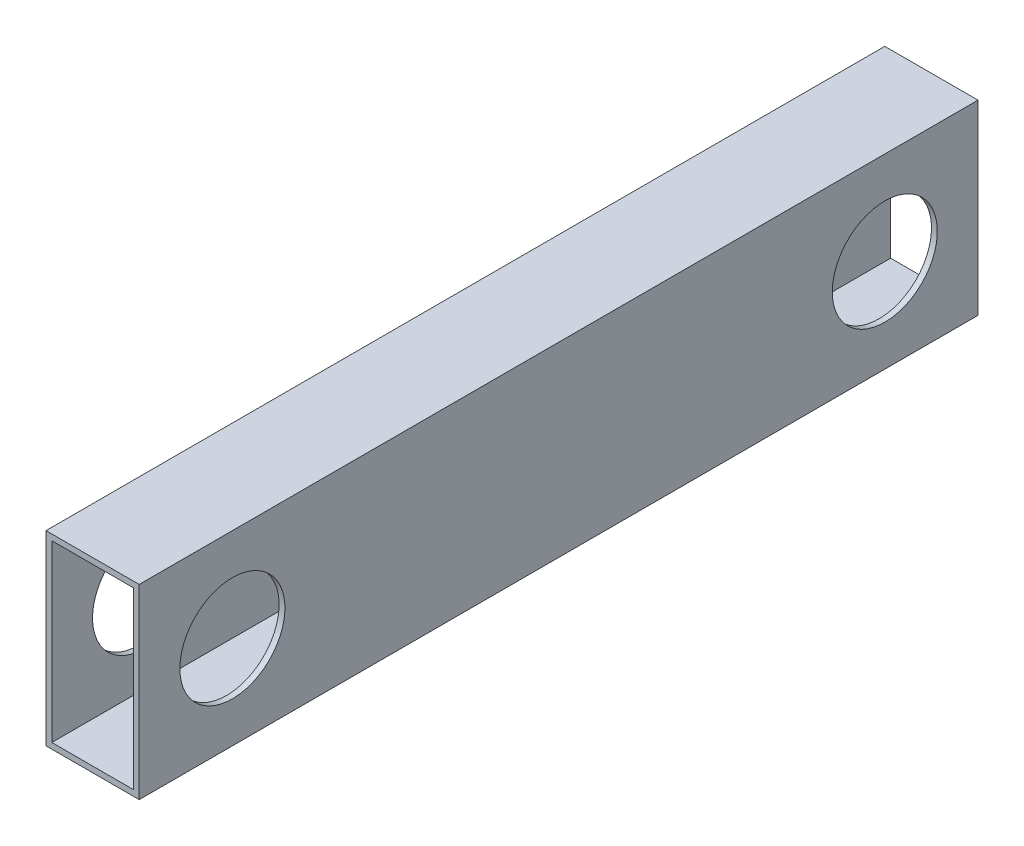
SolidWorks part; units mm, degrees
ref_plane "Front Plane" through (0, 0, 0) normal (0, 0, 1) x (1, 0, 0)
ref_plane "Top Plane" through (0, 0, 0) normal (0, 1, 0) x (1, 0, 0)
ref_plane "Right Plane" through (0, 0, 0) normal (1, 0, 0) x (0, 0, -1)
sketch "Sketch1" plane through (0, 0, 0) normal (0, 0, 1) x (1, 0, 0)
  line L0 (0, 0) -> (25.4, 50.8) construction
  line L1 (0, 0) -> (25.4, 0)
  line L2 (0, 0) -> (0, 50.8)
  line L3 (0, 50.8) -> (25.4, 50.8)
  line L4 (25.4, 0) -> (25.4, 50.8)
  line L6 (1.5875, 49.2125) -> (23.8125, 49.2125)
  line L7 (1.5875, 49.2125) -> (1.5875, 1.5875)
  line L8 (1.5875, 1.5875) -> (23.8125, 1.5875)
  line L9 (23.8125, 49.2125) -> (23.8125, 1.5875)
  line L10 (1.5875, 49.2125) -> (23.8125, 1.5875) construction
  line L11 (1.5875, 1.5875) -> (23.8125, 49.2125) construction
  point P5 (12.7, 25.4)
  point P6 (12.7, 25.4)
  dimension "D1" = 25.4
  dimension "D2" = 50.8
  dimension "D3" = 1.5875
  dimension "D4" = 1.5875
extrude "Boss-Extrude1" add sketch "Sketch1" along normal blind 228.6
sketch "Sketch2" plane through (25.4, 0, 0) normal (1, 0, 0) x (0, 0, -1)
  line L0 (0, 0) -> (0, 50.8) construction
  line L1 (-228.6, 50.8) -> (0, 50.8) construction
  line L2 (-114.3, 50.8) -> (-114.3, 104.8222) construction
  circle A0 centre (-25.4, 25.4) radius 14.3129
  circle A1 centre (-203.2, 25.4) radius 14.3129
  point P10 (-114.3, 50.8)
  point P11 (0, 0)
  dimension "D1" = 25.4
  dimension "D3" = 28.6258
  dimension "D2" = 25.4
extrude "Cut-Extrude1" cut sketch "Sketch2" against normal through all both and the other way through all
